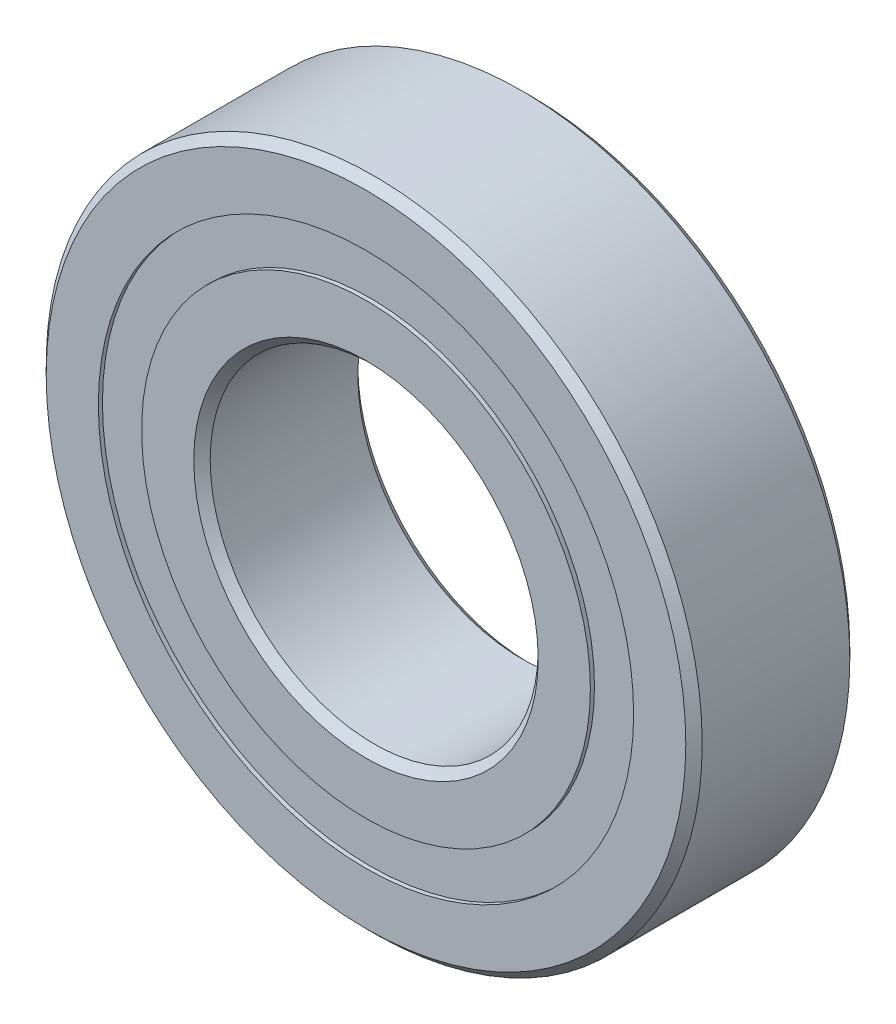
SolidWorks part; units mm, degrees
ref_plane "Front Plane" through (0, 0, 0) normal (0, 0, 1) x (1, 0, 0)
ref_plane "Top Plane" through (0, 0, 0) normal (0, 1, 0) x (1, 0, 0)
ref_plane "Right Plane" through (0, 0, 0) normal (1, 0, 0) x (0, 0, -1)
sketch "Sketch1" plane through (0, 0, 0) normal (1, 0, 0) x (0, 0, -1)
  line L0 (-6.35, 0) -> (6.35, 0) construction
  line L1 (0, 25.4) -> (0, -25.4) construction
  line L2 (5.715, 25.4) -> (-5.715, 25.4)
  line L3 (-5.715, 25.4) -> (-6.35, 24.765)
  line L4 (-6.35, 24.765) -> (-6.35, 20.7247)
  line L5 (-6.35, 20.7247) -> (-2.8222, 20.7247)
  line L6 (6.35, 20.7247) -> (2.8222, 20.7247)
  line L7 (6.35, 24.765) -> (6.35, 20.7247)
  line L8 (5.715, 25.4) -> (6.35, 24.765)
  line L9 (0, 25.4) -> (0, 19.05) construction
  line L10 (0, 19.05) -> (0, 12.7) construction
  arc A0 (-2.8222, 20.7247) -> (2.8222, 20.7247) centre (0, 19.05) cw
  point P14 (0, 12.7)
  dimension "D3" = 5.6444
  dimension "D1" = 45
  dimension "Width" = 12.7
  dimension "OD" = 50.8
  dimension "D2" = 0.635
  dimension "Shaft Dia" = 25.4
  dimension "D4" = 1.6747
revolve "Revolve1" add sketch "Sketch1" angle 360 about L0
sketch "Sketch3" plane through (0, 0, 0) normal (1, 0, 0) x (0, 0, -1)
  line L0 (-6.35, 17.3753) -> (-2.8222, 17.3753)
  line L1 (0, 25.4) -> (0, -25.4) construction
  line L2 (-6.35, 24.765) -> (-6.35, 20.7247) construction
  line L3 (-6.35, 17.3753) -> (-6.35, 13.335)
  line L4 (-5.715, 25.4) -> (-6.35, 24.765) construction
  line L5 (-6.35, 13.335) -> (-5.715, 12.7)
  line L6 (-5.715, 12.7) -> (5.715, 12.7)
  line L7 (5.715, 25.4) -> (5.715, -25.4) construction
  line L8 (5.715, 12.7) -> (6.35, 13.335)
  line L9 (6.35, -24.765) -> (6.35, 24.765) construction
  line L10 (6.35, 13.335) -> (6.35, 17.3753)
  line L11 (6.35, 17.3753) -> (2.8222, 17.3753)
  line L13 (5.715, 25.4) -> (6.35, 24.765) construction
  arc A0 (2.8222, 20.7247) -> (-2.8222, 20.7247) centre (0, 19.05) ccw construction
  arc A1 (2.8222, 17.3753) -> (-2.8222, 17.3753) centre (0, 19.05) cw
revolve "Revolve3" add sketch "Sketch3" angle 360 about L0
sketch "Sketch4" plane through (0, 0, 0) normal (1, 0, 0) x (0, 0, -1)
  line L0 (-3.2817, 19.05) -> (3.2817, 19.05)
  arc A2 (-3.2817, 19.05) -> (3.2817, 19.05) centre (0, 19.05) cw
  arc A3 (2.8222, 20.7247) -> (-2.8222, 20.7247) centre (0, 19.05) ccw construction
revolve "Revolve4" add sketch "Sketch4" angle 360 about L0
ref_axis "Axis1" through (0, 0, -6.35) along (0, 0, 1)
pattern_circular "CirPattern1" count 12 every 30 about axis through (0, 0, -6.35) along (0, 0, 1) of bodies 104
sketch "Sketch5" plane through (0, 0, 0) normal (1, 0, 0) x (0, 0, -1)
  line L0 (-6.35, 20.7247) -> (-2.8222, 20.7247) construction
  line L1 (-6.0325, 20.7247) -> (-3.2817, 20.7247)
  line L2 (-6.0325, 20.7247) -> (-6.0325, 17.3753)
  line L3 (-6.0325, 17.3753) -> (-3.2817, 17.3753)
  line L4 (-3.2817, 20.7247) -> (-3.2817, 17.3753)
  line L5 (-6.35, 17.3753) -> (-2.8222, 17.3753) construction
  line L6 (6.35, 20.7247) -> (2.8222, 20.7247) construction
  line L7 (6.0325, 20.7247) -> (3.2817, 20.7247)
  line L8 (6.0325, 20.7247) -> (6.0325, 17.3753)
  line L9 (6.0325, 17.3753) -> (3.2817, 17.3753)
  line L10 (3.2817, 20.7247) -> (3.2817, 17.3753)
  line L11 (6.35, 17.3753) -> (2.8222, 17.3753) construction
  line L12 (-5.715, 25.4) -> (-6.35, 24.765) construction
  point P18 (-6.0325, 25.0825)
revolve "Revolve5" add sketch "Sketch5" angle 360 about L0
equation "\"D2@Sketch1\" = \"Width@Sketch1\"*.05"
equation "\"D3@Sketch1\" = \"Width@Sketch1\"/2.25"
equation "\"D4@Sketch1\" = (((\"OD@Sketch1\"-\"Width@Sketch1\")/2)/3.25)/3.5"
equation "\"D2@CirPattern1\" = 360/\"Balls@CirPattern1\""
